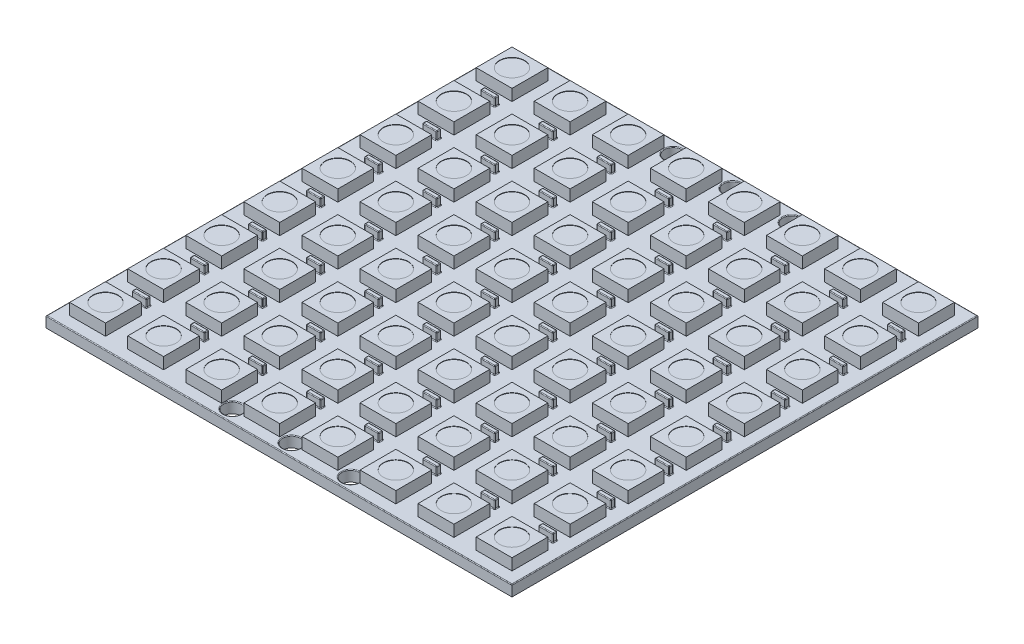
SolidWorks part; units mm, degrees
other "Cámara1"
ref_plane "Alzado" through (0, 0, 0) normal (0, 0, 1) x (1, 0, 0)
ref_plane "Planta" through (0, 0, 0) normal (0, 1, 0) x (1, 0, 0)
ref_plane "Vista lateral" through (0, 0, 0) normal (1, 0, 0) x (0, 0, -1)
sketch "Croquis1" plane through (0, 0, 0) normal (0, 1, 0) x (1, 0, 0)
  line L0 (24.25, 63.25) -> (32.5, 63.25) construction
  line L1 (0, 0) -> (65, 0)
  line L2 (0, 0) -> (0, 65)
  line L3 (0, 65) -> (65, 65)
  line L4 (65, 0) -> (65, 65)
  line L5 (32.5, 63.25) -> (40.75, 63.25) construction
  line L6 (32.5, 65) -> (32.5, 63.25) construction
  line L7 (0, 32.5) -> (65, 32.5) construction
  circle A0 centre (24.25, 63.25) radius 1.25
  circle A1 centre (32.5, 63.25) radius 1.25
  circle A2 centre (40.75, 63.25) radius 1.25
  circle A3 centre (32.5, 1.75) radius 1.25
  circle A4 centre (40.75, 1.75) radius 1.25
  circle A5 centre (24.25, 1.75) radius 1.25
  dimension "D2" = 2.5
  dimension "D4" = 24.25
  dimension "D5" = 24.25
  dimension "D1" = 65
  dimension "D3" = 1.75
extrude "Saliente-Extruir1" add sketch "Croquis1" along normal blind 1.5
sketch "Croquis2" plane through (0, 1.5, 0) normal (0, 1, 0) x (1, 0, 0)
  line L0 (0, 65) -> (0, 0) construction
  line L1 (1.65, 6.65) -> (6.65, 6.65)
  line L2 (1.65, 6.65) -> (1.65, 1.65)
  line L3 (1.65, 1.65) -> (6.65, 1.65)
  line L4 (6.65, 6.65) -> (6.65, 1.65)
  line L5 (0, 0) -> (65, 0) construction
  line L6 (9.75, 6.65) -> (9.75, 1.65)
  line L7 (9.75, 6.65) -> (14.75, 6.65)
  line L8 (14.75, 6.65) -> (14.75, 1.65)
  line L9 (9.75, 1.65) -> (14.75, 1.65)
  line L10 (17.85, 6.65) -> (17.85, 1.65)
  line L11 (17.85, 6.65) -> (22.85, 6.65)
  line L12 (22.85, 6.65) -> (22.85, 1.65)
  line L13 (17.85, 1.65) -> (22.85, 1.65)
  line L14 (25.95, 6.65) -> (25.95, 1.65)
  line L15 (25.95, 6.65) -> (30.95, 6.65)
  line L16 (30.95, 6.65) -> (30.95, 1.65)
  line L17 (25.95, 1.65) -> (30.95, 1.65)
  line L18 (34.05, 6.65) -> (34.05, 1.65)
  line L19 (34.05, 6.65) -> (39.05, 6.65)
  line L20 (39.05, 6.65) -> (39.05, 1.65)
  line L21 (34.05, 1.65) -> (39.05, 1.65)
  line L22 (42.15, 6.65) -> (42.15, 1.65)
  line L23 (42.15, 6.65) -> (47.15, 6.65)
  line L24 (47.15, 6.65) -> (47.15, 1.65)
  line L25 (42.15, 1.65) -> (47.15, 1.65)
  line L26 (50.25, 6.65) -> (50.25, 1.65)
  line L27 (50.25, 6.65) -> (55.25, 6.65)
  line L28 (55.25, 6.65) -> (55.25, 1.65)
  line L29 (50.25, 1.65) -> (55.25, 1.65)
  line L30 (58.35, 6.65) -> (58.35, 1.65)
  line L31 (58.35, 6.65) -> (63.35, 6.65)
  line L32 (63.35, 6.65) -> (63.35, 1.65)
  line L33 (58.35, 1.65) -> (63.35, 1.65)
  line L34 (9.75, 14.75) -> (9.75, 9.75)
  line L35 (9.75, 14.75) -> (14.75, 14.75)
  line L36 (14.75, 14.75) -> (14.75, 9.75)
  line L37 (9.75, 9.75) -> (14.75, 9.75)
  line L38 (17.85, 14.75) -> (17.85, 9.75)
  line L39 (17.85, 14.75) -> (22.85, 14.75)
  line L40 (22.85, 14.75) -> (22.85, 9.75)
  line L41 (17.85, 9.75) -> (22.85, 9.75)
  line L42 (25.95, 14.75) -> (25.95, 9.75)
  line L43 (25.95, 14.75) -> (30.95, 14.75)
  line L44 (30.95, 14.75) -> (30.95, 9.75)
  line L45 (25.95, 9.75) -> (30.95, 9.75)
  line L46 (34.05, 14.75) -> (34.05, 9.75)
  line L47 (34.05, 14.75) -> (39.05, 14.75)
  line L48 (39.05, 14.75) -> (39.05, 9.75)
  line L49 (34.05, 9.75) -> (39.05, 9.75)
  line L50 (42.15, 14.75) -> (42.15, 9.75)
  line L51 (42.15, 14.75) -> (47.15, 14.75)
  line L52 (47.15, 14.75) -> (47.15, 9.75)
  line L53 (42.15, 9.75) -> (47.15, 9.75)
  line L54 (50.25, 14.75) -> (50.25, 9.75)
  line L55 (50.25, 14.75) -> (55.25, 14.75)
  line L56 (55.25, 14.75) -> (55.25, 9.75)
  line L57 (50.25, 9.75) -> (55.25, 9.75)
  line L58 (58.35, 14.75) -> (58.35, 9.75)
  line L59 (58.35, 14.75) -> (63.35, 14.75)
  line L60 (63.35, 14.75) -> (63.35, 9.75)
  line L61 (58.35, 9.75) -> (63.35, 9.75)
  line L62 (9.75, 22.85) -> (9.75, 17.85)
  line L63 (9.75, 22.85) -> (14.75, 22.85)
  line L64 (14.75, 22.85) -> (14.75, 17.85)
  line L65 (9.75, 17.85) -> (14.75, 17.85)
  line L66 (17.85, 22.85) -> (17.85, 17.85)
  line L67 (17.85, 22.85) -> (22.85, 22.85)
  line L68 (22.85, 22.85) -> (22.85, 17.85)
  line L69 (17.85, 17.85) -> (22.85, 17.85)
  line L70 (25.95, 22.85) -> (25.95, 17.85)
  line L71 (25.95, 22.85) -> (30.95, 22.85)
  line L72 (30.95, 22.85) -> (30.95, 17.85)
  line L73 (25.95, 17.85) -> (30.95, 17.85)
  line L74 (34.05, 22.85) -> (34.05, 17.85)
  line L75 (34.05, 22.85) -> (39.05, 22.85)
  line L76 (39.05, 22.85) -> (39.05, 17.85)
  line L77 (34.05, 17.85) -> (39.05, 17.85)
  line L78 (42.15, 22.85) -> (42.15, 17.85)
  line L79 (42.15, 22.85) -> (47.15, 22.85)
  line L80 (47.15, 22.85) -> (47.15, 17.85)
  line L81 (42.15, 17.85) -> (47.15, 17.85)
  line L82 (50.25, 22.85) -> (50.25, 17.85)
  line L83 (50.25, 22.85) -> (55.25, 22.85)
  line L84 (55.25, 22.85) -> (55.25, 17.85)
  line L85 (50.25, 17.85) -> (55.25, 17.85)
  line L86 (58.35, 22.85) -> (58.35, 17.85)
  line L87 (58.35, 22.85) -> (63.35, 22.85)
  line L88 (63.35, 22.85) -> (63.35, 17.85)
  line L89 (58.35, 17.85) -> (63.35, 17.85)
  line L90 (9.75, 30.95) -> (9.75, 25.95)
  line L91 (9.75, 30.95) -> (14.75, 30.95)
  line L92 (14.75, 30.95) -> (14.75, 25.95)
  line L93 (9.75, 25.95) -> (14.75, 25.95)
  line L94 (17.85, 30.95) -> (17.85, 25.95)
  line L95 (17.85, 30.95) -> (22.85, 30.95)
  line L96 (22.85, 30.95) -> (22.85, 25.95)
  line L97 (17.85, 25.95) -> (22.85, 25.95)
  line L98 (25.95, 30.95) -> (25.95, 25.95)
  line L99 (25.95, 30.95) -> (30.95, 30.95)
  line L100 (30.95, 30.95) -> (30.95, 25.95)
  line L101 (25.95, 25.95) -> (30.95, 25.95)
  line L102 (34.05, 30.95) -> (34.05, 25.95)
  line L103 (34.05, 30.95) -> (39.05, 30.95)
  line L104 (39.05, 30.95) -> (39.05, 25.95)
  line L105 (34.05, 25.95) -> (39.05, 25.95)
  line L106 (42.15, 30.95) -> (42.15, 25.95)
  line L107 (42.15, 30.95) -> (47.15, 30.95)
  line L108 (47.15, 30.95) -> (47.15, 25.95)
  line L109 (42.15, 25.95) -> (47.15, 25.95)
  line L110 (50.25, 30.95) -> (50.25, 25.95)
  line L111 (50.25, 30.95) -> (55.25, 30.95)
  line L112 (55.25, 30.95) -> (55.25, 25.95)
  line L113 (50.25, 25.95) -> (55.25, 25.95)
  line L114 (58.35, 30.95) -> (58.35, 25.95)
  line L115 (58.35, 30.95) -> (63.35, 30.95)
  line L116 (63.35, 30.95) -> (63.35, 25.95)
  line L117 (58.35, 25.95) -> (63.35, 25.95)
  line L118 (9.75, 39.05) -> (9.75, 34.05)
  line L119 (9.75, 39.05) -> (14.75, 39.05)
  line L120 (14.75, 39.05) -> (14.75, 34.05)
  line L121 (9.75, 34.05) -> (14.75, 34.05)
  line L122 (17.85, 39.05) -> (17.85, 34.05)
  line L123 (17.85, 39.05) -> (22.85, 39.05)
  line L124 (22.85, 39.05) -> (22.85, 34.05)
  line L125 (17.85, 34.05) -> (22.85, 34.05)
  line L126 (25.95, 39.05) -> (25.95, 34.05)
  line L127 (25.95, 39.05) -> (30.95, 39.05)
  line L128 (30.95, 39.05) -> (30.95, 34.05)
  line L129 (25.95, 34.05) -> (30.95, 34.05)
  line L130 (34.05, 39.05) -> (34.05, 34.05)
  line L131 (34.05, 39.05) -> (39.05, 39.05)
  line L132 (39.05, 39.05) -> (39.05, 34.05)
  line L133 (34.05, 34.05) -> (39.05, 34.05)
  line L134 (42.15, 39.05) -> (42.15, 34.05)
  line L135 (42.15, 39.05) -> (47.15, 39.05)
  line L136 (47.15, 39.05) -> (47.15, 34.05)
  line L137 (42.15, 34.05) -> (47.15, 34.05)
  line L138 (50.25, 39.05) -> (50.25, 34.05)
  line L139 (50.25, 39.05) -> (55.25, 39.05)
  line L140 (55.25, 39.05) -> (55.25, 34.05)
  line L141 (50.25, 34.05) -> (55.25, 34.05)
  line L142 (58.35, 39.05) -> (58.35, 34.05)
  line L143 (58.35, 39.05) -> (63.35, 39.05)
  line L144 (63.35, 39.05) -> (63.35, 34.05)
  line L145 (58.35, 34.05) -> (63.35, 34.05)
  line L146 (9.75, 47.15) -> (9.75, 42.15)
  line L147 (9.75, 47.15) -> (14.75, 47.15)
  line L148 (14.75, 47.15) -> (14.75, 42.15)
  line L149 (9.75, 42.15) -> (14.75, 42.15)
  line L150 (17.85, 47.15) -> (17.85, 42.15)
  line L151 (17.85, 47.15) -> (22.85, 47.15)
  line L152 (22.85, 47.15) -> (22.85, 42.15)
  line L153 (17.85, 42.15) -> (22.85, 42.15)
  line L154 (25.95, 47.15) -> (25.95, 42.15)
  line L155 (25.95, 47.15) -> (30.95, 47.15)
  line L156 (30.95, 47.15) -> (30.95, 42.15)
  line L157 (25.95, 42.15) -> (30.95, 42.15)
  line L158 (34.05, 47.15) -> (34.05, 42.15)
  line L159 (34.05, 47.15) -> (39.05, 47.15)
  line L160 (39.05, 47.15) -> (39.05, 42.15)
  line L161 (34.05, 42.15) -> (39.05, 42.15)
  line L162 (42.15, 47.15) -> (42.15, 42.15)
  line L163 (42.15, 47.15) -> (47.15, 47.15)
  line L164 (47.15, 47.15) -> (47.15, 42.15)
  line L165 (42.15, 42.15) -> (47.15, 42.15)
  line L166 (50.25, 47.15) -> (50.25, 42.15)
  line L167 (50.25, 47.15) -> (55.25, 47.15)
  line L168 (55.25, 47.15) -> (55.25, 42.15)
  line L169 (50.25, 42.15) -> (55.25, 42.15)
  line L170 (58.35, 47.15) -> (58.35, 42.15)
  line L171 (58.35, 47.15) -> (63.35, 47.15)
  line L172 (63.35, 47.15) -> (63.35, 42.15)
  line L173 (58.35, 42.15) -> (63.35, 42.15)
  line L174 (9.75, 55.25) -> (9.75, 50.25)
  line L175 (9.75, 55.25) -> (14.75, 55.25)
  line L176 (14.75, 55.25) -> (14.75, 50.25)
  line L177 (9.75, 50.25) -> (14.75, 50.25)
  line L178 (17.85, 55.25) -> (17.85, 50.25)
  line L179 (17.85, 55.25) -> (22.85, 55.25)
  line L180 (22.85, 55.25) -> (22.85, 50.25)
  line L181 (17.85, 50.25) -> (22.85, 50.25)
  line L182 (25.95, 55.25) -> (25.95, 50.25)
  line L183 (25.95, 55.25) -> (30.95, 55.25)
  line L184 (30.95, 55.25) -> (30.95, 50.25)
  line L185 (25.95, 50.25) -> (30.95, 50.25)
  line L186 (34.05, 55.25) -> (34.05, 50.25)
  line L187 (34.05, 55.25) -> (39.05, 55.25)
  line L188 (39.05, 55.25) -> (39.05, 50.25)
  line L189 (34.05, 50.25) -> (39.05, 50.25)
  line L190 (42.15, 55.25) -> (42.15, 50.25)
  line L191 (42.15, 55.25) -> (47.15, 55.25)
  line L192 (47.15, 55.25) -> (47.15, 50.25)
  line L193 (42.15, 50.25) -> (47.15, 50.25)
  line L194 (50.25, 55.25) -> (50.25, 50.25)
  line L195 (50.25, 55.25) -> (55.25, 55.25)
  line L196 (55.25, 55.25) -> (55.25, 50.25)
  line L197 (50.25, 50.25) -> (55.25, 50.25)
  line L198 (58.35, 55.25) -> (58.35, 50.25)
  line L199 (58.35, 55.25) -> (63.35, 55.25)
  line L200 (63.35, 55.25) -> (63.35, 50.25)
  line L201 (58.35, 50.25) -> (63.35, 50.25)
  line L202 (9.75, 63.35) -> (9.75, 58.35)
  line L203 (9.75, 63.35) -> (14.75, 63.35)
  line L204 (14.75, 63.35) -> (14.75, 58.35)
  line L205 (9.75, 58.35) -> (14.75, 58.35)
  line L206 (17.85, 63.35) -> (17.85, 58.35)
  line L207 (17.85, 63.35) -> (22.85, 63.35)
  line L208 (22.85, 63.35) -> (22.85, 58.35)
  line L209 (17.85, 58.35) -> (22.85, 58.35)
  line L210 (25.95, 63.35) -> (25.95, 58.35)
  line L211 (25.95, 63.35) -> (30.95, 63.35)
  line L212 (30.95, 63.35) -> (30.95, 58.35)
  line L213 (25.95, 58.35) -> (30.95, 58.35)
  line L214 (34.05, 63.35) -> (34.05, 58.35)
  line L215 (34.05, 63.35) -> (39.05, 63.35)
  line L216 (39.05, 63.35) -> (39.05, 58.35)
  line L217 (34.05, 58.35) -> (39.05, 58.35)
  line L218 (42.15, 63.35) -> (42.15, 58.35)
  line L219 (42.15, 63.35) -> (47.15, 63.35)
  line L220 (47.15, 63.35) -> (47.15, 58.35)
  line L221 (42.15, 58.35) -> (47.15, 58.35)
  line L222 (50.25, 63.35) -> (50.25, 58.35)
  line L223 (50.25, 63.35) -> (55.25, 63.35)
  line L224 (55.25, 63.35) -> (55.25, 58.35)
  line L225 (50.25, 58.35) -> (55.25, 58.35)
  line L226 (58.35, 63.35) -> (58.35, 58.35)
  line L227 (58.35, 63.35) -> (63.35, 63.35)
  line L228 (63.35, 63.35) -> (63.35, 58.35)
  line L229 (58.35, 58.35) -> (63.35, 58.35)
  line L230 (1.65, 14.75) -> (1.65, 9.75)
  line L231 (1.65, 14.75) -> (6.65, 14.75)
  line L232 (6.65, 14.75) -> (6.65, 9.75)
  line L233 (1.65, 9.75) -> (6.65, 9.75)
  line L234 (1.65, 22.85) -> (1.65, 17.85)
  line L235 (1.65, 22.85) -> (6.65, 22.85)
  line L236 (6.65, 22.85) -> (6.65, 17.85)
  line L237 (1.65, 17.85) -> (6.65, 17.85)
  line L238 (1.65, 30.95) -> (1.65, 25.95)
  line L239 (1.65, 30.95) -> (6.65, 30.95)
  line L240 (6.65, 30.95) -> (6.65, 25.95)
  line L241 (1.65, 25.95) -> (6.65, 25.95)
  line L242 (1.65, 39.05) -> (1.65, 34.05)
  line L243 (1.65, 39.05) -> (6.65, 39.05)
  line L244 (6.65, 39.05) -> (6.65, 34.05)
  line L245 (1.65, 34.05) -> (6.65, 34.05)
  line L246 (1.65, 47.15) -> (1.65, 42.15)
  line L247 (1.65, 47.15) -> (6.65, 47.15)
  line L248 (6.65, 47.15) -> (6.65, 42.15)
  line L249 (1.65, 42.15) -> (6.65, 42.15)
  line L250 (1.65, 55.25) -> (1.65, 50.25)
  line L251 (1.65, 55.25) -> (6.65, 55.25)
  line L252 (6.65, 55.25) -> (6.65, 50.25)
  line L253 (1.65, 50.25) -> (6.65, 50.25)
  line L254 (1.65, 63.35) -> (1.65, 58.35)
  line L255 (1.65, 63.35) -> (6.65, 63.35)
  line L256 (6.65, 63.35) -> (6.65, 58.35)
  line L257 (1.65, 58.35) -> (6.65, 58.35)
  dimension "D1" = 5
  dimension "D2" = 1.65
  dimension "D3" = 1.65
  dimension "D4" = 8
  dimension "D5" = 8
extrude "Saliente-Extruir2" add sketch "Croquis2" along normal blind 1.6 separate body
sketch "Croquis3" plane through (0, 3.1, 0) normal (0, 1, 0) x (1, 0, 0)
  line L0 (4.15, 4.15) -> (12.25, 4.15) construction
  line L1 (4.15, 4.15) -> (4.15, 12.25) construction
  circle A0 centre (4.15, 4.15) radius 1.75
  circle A1 centre (12.25, 4.15) radius 1.75
  circle A2 centre (20.35, 4.15) radius 1.75
  circle A3 centre (28.45, 4.15) radius 1.75
  circle A4 centre (36.55, 4.15) radius 1.75
  circle A5 centre (44.65, 4.15) radius 1.75
  circle A6 centre (52.75, 4.15) radius 1.75
  circle A7 centre (60.85, 4.15) radius 1.75
  circle A8 centre (12.25, 12.25) radius 1.75
  circle A9 centre (20.35, 12.25) radius 1.75
  circle A10 centre (28.45, 12.25) radius 1.75
  circle A11 centre (36.55, 12.25) radius 1.75
  circle A12 centre (44.65, 12.25) radius 1.75
  circle A13 centre (52.75, 12.25) radius 1.75
  circle A14 centre (60.85, 12.25) radius 1.75
  circle A15 centre (12.25, 20.35) radius 1.75
  circle A16 centre (20.35, 20.35) radius 1.75
  circle A17 centre (28.45, 20.35) radius 1.75
  circle A18 centre (36.55, 20.35) radius 1.75
  circle A19 centre (44.65, 20.35) radius 1.75
  circle A20 centre (52.75, 20.35) radius 1.75
  circle A21 centre (60.85, 20.35) radius 1.75
  circle A22 centre (12.25, 28.45) radius 1.75
  circle A23 centre (20.35, 28.45) radius 1.75
  circle A24 centre (28.45, 28.45) radius 1.75
  circle A25 centre (36.55, 28.45) radius 1.75
  circle A26 centre (44.65, 28.45) radius 1.75
  circle A27 centre (52.75, 28.45) radius 1.75
  circle A28 centre (60.85, 28.45) radius 1.75
  circle A29 centre (12.25, 36.55) radius 1.75
  circle A30 centre (20.35, 36.55) radius 1.75
  circle A31 centre (28.45, 36.55) radius 1.75
  circle A32 centre (36.55, 36.55) radius 1.75
  circle A33 centre (44.65, 36.55) radius 1.75
  circle A34 centre (52.75, 36.55) radius 1.75
  circle A35 centre (60.85, 36.55) radius 1.75
  circle A36 centre (12.25, 44.65) radius 1.75
  circle A37 centre (20.35, 44.65) radius 1.75
  circle A38 centre (28.45, 44.65) radius 1.75
  circle A39 centre (36.55, 44.65) radius 1.75
  circle A40 centre (44.65, 44.65) radius 1.75
  circle A41 centre (52.75, 44.65) radius 1.75
  circle A42 centre (60.85, 44.65) radius 1.75
  circle A43 centre (12.25, 52.75) radius 1.75
  circle A44 centre (20.35, 52.75) radius 1.75
  circle A45 centre (28.45, 52.75) radius 1.75
  circle A46 centre (36.55, 52.75) radius 1.75
  circle A47 centre (44.65, 52.75) radius 1.75
  circle A48 centre (52.75, 52.75) radius 1.75
  circle A49 centre (60.85, 52.75) radius 1.75
  circle A50 centre (12.25, 60.85) radius 1.75
  circle A51 centre (20.35, 60.85) radius 1.75
  circle A52 centre (28.45, 60.85) radius 1.75
  circle A53 centre (36.55, 60.85) radius 1.75
  circle A54 centre (44.65, 60.85) radius 1.75
  circle A55 centre (52.75, 60.85) radius 1.75
  circle A56 centre (60.85, 60.85) radius 1.75
  circle A57 centre (4.15, 12.25) radius 1.75
  circle A58 centre (4.15, 20.35) radius 1.75
  circle A59 centre (4.15, 28.45) radius 1.75
  circle A60 centre (4.15, 36.55) radius 1.75
  circle A61 centre (4.15, 44.65) radius 1.75
  circle A62 centre (4.15, 52.75) radius 1.75
  circle A63 centre (4.15, 60.85) radius 1.75
  dimension "D1" = 3.5
  dimension "D4" = 8.1
  dimension "D5" = 8.1
  dimension "D2" = 8
  dimension "D3" = 8
extrude "Cortar-Extruir1" cut sketch "Croquis3" against normal blind 0.05
sketch "Croquis4" plane through (0, 1.5, 0) normal (0, 1, 0) x (1, 0, 0)
  line L0 (6.65, 9.75) -> (6.65, 6.65) construction
  line L1 (6.65, 8.2) -> (0, 8.2) construction
  line L2 (0, 65) -> (0, 0) construction
  line L3 (12.2, 7.9) -> (12.2, 8.5)
  line L4 (4.1, 7.9) -> (6.1, 7.9)
  line L5 (4.1, 7.9) -> (4.1, 8.5)
  line L6 (4.1, 8.5) -> (6.1, 8.5)
  line L7 (6.1, 7.9) -> (6.1, 8.5)
  line L8 (5.1, 8.5) -> (5.1, 7.9) construction
  line L9 (4.1, 8.2) -> (6.65, 8.2) construction
  line L10 (12.2, 7.9) -> (14.2, 7.9)
  line L11 (14.2, 7.9) -> (14.2, 8.5)
  line L12 (12.2, 8.5) -> (14.2, 8.5)
  line L13 (20.3, 7.9) -> (20.3, 8.5)
  line L14 (20.3, 7.9) -> (22.3, 7.9)
  line L15 (22.3, 7.9) -> (22.3, 8.5)
  line L16 (20.3, 8.5) -> (22.3, 8.5)
  line L17 (28.4, 7.9) -> (28.4, 8.5)
  line L18 (28.4, 7.9) -> (30.4, 7.9)
  line L19 (30.4, 7.9) -> (30.4, 8.5)
  line L20 (28.4, 8.5) -> (30.4, 8.5)
  line L21 (36.5, 7.9) -> (36.5, 8.5)
  line L22 (36.5, 7.9) -> (38.5, 7.9)
  line L23 (38.5, 7.9) -> (38.5, 8.5)
  line L24 (36.5, 8.5) -> (38.5, 8.5)
  line L25 (44.6, 7.9) -> (44.6, 8.5)
  line L26 (44.6, 7.9) -> (46.6, 7.9)
  line L27 (46.6, 7.9) -> (46.6, 8.5)
  line L28 (44.6, 8.5) -> (46.6, 8.5)
  line L29 (52.7, 7.9) -> (52.7, 8.5)
  line L30 (52.7, 7.9) -> (54.7, 7.9)
  line L31 (54.7, 7.9) -> (54.7, 8.5)
  line L32 (52.7, 8.5) -> (54.7, 8.5)
  line L33 (60.8, 7.9) -> (60.8, 8.5)
  line L34 (60.8, 7.9) -> (62.8, 7.9)
  line L35 (62.8, 7.9) -> (62.8, 8.5)
  line L36 (60.8, 8.5) -> (62.8, 8.5)
  line L37 (12.2, 16) -> (12.2, 16.6)
  line L38 (12.2, 16) -> (14.2, 16)
  line L39 (14.2, 16) -> (14.2, 16.6)
  line L40 (12.2, 16.6) -> (14.2, 16.6)
  line L41 (20.3, 16) -> (20.3, 16.6)
  line L42 (20.3, 16) -> (22.3, 16)
  line L43 (22.3, 16) -> (22.3, 16.6)
  line L44 (20.3, 16.6) -> (22.3, 16.6)
  line L45 (28.4, 16) -> (28.4, 16.6)
  line L46 (28.4, 16) -> (30.4, 16)
  line L47 (30.4, 16) -> (30.4, 16.6)
  line L48 (28.4, 16.6) -> (30.4, 16.6)
  line L49 (36.5, 16) -> (36.5, 16.6)
  line L50 (36.5, 16) -> (38.5, 16)
  line L51 (38.5, 16) -> (38.5, 16.6)
  line L52 (36.5, 16.6) -> (38.5, 16.6)
  line L53 (44.6, 16) -> (44.6, 16.6)
  line L54 (44.6, 16) -> (46.6, 16)
  line L55 (46.6, 16) -> (46.6, 16.6)
  line L56 (44.6, 16.6) -> (46.6, 16.6)
  line L57 (52.7, 16) -> (52.7, 16.6)
  line L58 (52.7, 16) -> (54.7, 16)
  line L59 (54.7, 16) -> (54.7, 16.6)
  line L60 (52.7, 16.6) -> (54.7, 16.6)
  line L61 (60.8, 16) -> (60.8, 16.6)
  line L62 (60.8, 16) -> (62.8, 16)
  line L63 (62.8, 16) -> (62.8, 16.6)
  line L64 (60.8, 16.6) -> (62.8, 16.6)
  line L65 (12.2, 24.1) -> (12.2, 24.7)
  line L66 (12.2, 24.1) -> (14.2, 24.1)
  line L67 (14.2, 24.1) -> (14.2, 24.7)
  line L68 (12.2, 24.7) -> (14.2, 24.7)
  line L69 (20.3, 24.1) -> (20.3, 24.7)
  line L70 (20.3, 24.1) -> (22.3, 24.1)
  line L71 (22.3, 24.1) -> (22.3, 24.7)
  line L72 (20.3, 24.7) -> (22.3, 24.7)
  line L73 (28.4, 24.1) -> (28.4, 24.7)
  line L74 (28.4, 24.1) -> (30.4, 24.1)
  line L75 (30.4, 24.1) -> (30.4, 24.7)
  line L76 (28.4, 24.7) -> (30.4, 24.7)
  line L77 (36.5, 24.1) -> (36.5, 24.7)
  line L78 (36.5, 24.1) -> (38.5, 24.1)
  line L79 (38.5, 24.1) -> (38.5, 24.7)
  line L80 (36.5, 24.7) -> (38.5, 24.7)
  line L81 (44.6, 24.1) -> (44.6, 24.7)
  line L82 (44.6, 24.1) -> (46.6, 24.1)
  line L83 (46.6, 24.1) -> (46.6, 24.7)
  line L84 (44.6, 24.7) -> (46.6, 24.7)
  line L85 (52.7, 24.1) -> (52.7, 24.7)
  line L86 (52.7, 24.1) -> (54.7, 24.1)
  line L87 (54.7, 24.1) -> (54.7, 24.7)
  line L88 (52.7, 24.7) -> (54.7, 24.7)
  line L89 (60.8, 24.1) -> (60.8, 24.7)
  line L90 (60.8, 24.1) -> (62.8, 24.1)
  line L91 (62.8, 24.1) -> (62.8, 24.7)
  line L92 (60.8, 24.7) -> (62.8, 24.7)
  line L93 (12.2, 32.2) -> (12.2, 32.8)
  line L94 (12.2, 32.2) -> (14.2, 32.2)
  line L95 (14.2, 32.2) -> (14.2, 32.8)
  line L96 (12.2, 32.8) -> (14.2, 32.8)
  line L97 (20.3, 32.2) -> (20.3, 32.8)
  line L98 (20.3, 32.2) -> (22.3, 32.2)
  line L99 (22.3, 32.2) -> (22.3, 32.8)
  line L100 (20.3, 32.8) -> (22.3, 32.8)
  line L101 (28.4, 32.2) -> (28.4, 32.8)
  line L102 (28.4, 32.2) -> (30.4, 32.2)
  line L103 (30.4, 32.2) -> (30.4, 32.8)
  line L104 (28.4, 32.8) -> (30.4, 32.8)
  line L105 (36.5, 32.2) -> (36.5, 32.8)
  line L106 (36.5, 32.2) -> (38.5, 32.2)
  line L107 (38.5, 32.2) -> (38.5, 32.8)
  line L108 (36.5, 32.8) -> (38.5, 32.8)
  line L109 (44.6, 32.2) -> (44.6, 32.8)
  line L110 (44.6, 32.2) -> (46.6, 32.2)
  line L111 (46.6, 32.2) -> (46.6, 32.8)
  line L112 (44.6, 32.8) -> (46.6, 32.8)
  line L113 (52.7, 32.2) -> (52.7, 32.8)
  line L114 (52.7, 32.2) -> (54.7, 32.2)
  line L115 (54.7, 32.2) -> (54.7, 32.8)
  line L116 (52.7, 32.8) -> (54.7, 32.8)
  line L117 (60.8, 32.2) -> (60.8, 32.8)
  line L118 (60.8, 32.2) -> (62.8, 32.2)
  line L119 (62.8, 32.2) -> (62.8, 32.8)
  line L120 (60.8, 32.8) -> (62.8, 32.8)
  line L121 (12.2, 40.3) -> (12.2, 40.9)
  line L122 (12.2, 40.3) -> (14.2, 40.3)
  line L123 (14.2, 40.3) -> (14.2, 40.9)
  line L124 (12.2, 40.9) -> (14.2, 40.9)
  line L125 (20.3, 40.3) -> (20.3, 40.9)
  line L126 (20.3, 40.3) -> (22.3, 40.3)
  line L127 (22.3, 40.3) -> (22.3, 40.9)
  line L128 (20.3, 40.9) -> (22.3, 40.9)
  line L129 (28.4, 40.3) -> (28.4, 40.9)
  line L130 (28.4, 40.3) -> (30.4, 40.3)
  line L131 (30.4, 40.3) -> (30.4, 40.9)
  line L132 (28.4, 40.9) -> (30.4, 40.9)
  line L133 (36.5, 40.3) -> (36.5, 40.9)
  line L134 (36.5, 40.3) -> (38.5, 40.3)
  line L135 (38.5, 40.3) -> (38.5, 40.9)
  line L136 (36.5, 40.9) -> (38.5, 40.9)
  line L137 (44.6, 40.3) -> (44.6, 40.9)
  line L138 (44.6, 40.3) -> (46.6, 40.3)
  line L139 (46.6, 40.3) -> (46.6, 40.9)
  line L140 (44.6, 40.9) -> (46.6, 40.9)
  line L141 (52.7, 40.3) -> (52.7, 40.9)
  line L142 (52.7, 40.3) -> (54.7, 40.3)
  line L143 (54.7, 40.3) -> (54.7, 40.9)
  line L144 (52.7, 40.9) -> (54.7, 40.9)
  line L145 (60.8, 40.3) -> (60.8, 40.9)
  line L146 (60.8, 40.3) -> (62.8, 40.3)
  line L147 (62.8, 40.3) -> (62.8, 40.9)
  line L148 (60.8, 40.9) -> (62.8, 40.9)
  line L149 (12.2, 48.4) -> (12.2, 49)
  line L150 (12.2, 48.4) -> (14.2, 48.4)
  line L151 (14.2, 48.4) -> (14.2, 49)
  line L152 (12.2, 49) -> (14.2, 49)
  line L153 (20.3, 48.4) -> (20.3, 49)
  line L154 (20.3, 48.4) -> (22.3, 48.4)
  line L155 (22.3, 48.4) -> (22.3, 49)
  line L156 (20.3, 49) -> (22.3, 49)
  line L157 (28.4, 48.4) -> (28.4, 49)
  line L158 (28.4, 48.4) -> (30.4, 48.4)
  line L159 (30.4, 48.4) -> (30.4, 49)
  line L160 (28.4, 49) -> (30.4, 49)
  line L161 (36.5, 48.4) -> (36.5, 49)
  line L162 (36.5, 48.4) -> (38.5, 48.4)
  line L163 (38.5, 48.4) -> (38.5, 49)
  line L164 (36.5, 49) -> (38.5, 49)
  line L165 (44.6, 48.4) -> (44.6, 49)
  line L166 (44.6, 48.4) -> (46.6, 48.4)
  line L167 (46.6, 48.4) -> (46.6, 49)
  line L168 (44.6, 49) -> (46.6, 49)
  line L169 (52.7, 48.4) -> (52.7, 49)
  line L170 (52.7, 48.4) -> (54.7, 48.4)
  line L171 (54.7, 48.4) -> (54.7, 49)
  line L172 (52.7, 49) -> (54.7, 49)
  line L173 (60.8, 48.4) -> (60.8, 49)
  line L174 (60.8, 48.4) -> (62.8, 48.4)
  line L175 (62.8, 48.4) -> (62.8, 49)
  line L176 (60.8, 49) -> (62.8, 49)
  line L177 (12.2, 56.5) -> (12.2, 57.1)
  line L178 (12.2, 56.5) -> (14.2, 56.5)
  line L179 (14.2, 56.5) -> (14.2, 57.1)
  line L180 (12.2, 57.1) -> (14.2, 57.1)
  line L181 (20.3, 56.5) -> (20.3, 57.1)
  line L182 (20.3, 56.5) -> (22.3, 56.5)
  line L183 (22.3, 56.5) -> (22.3, 57.1)
  line L184 (20.3, 57.1) -> (22.3, 57.1)
  line L185 (28.4, 56.5) -> (28.4, 57.1)
  line L186 (28.4, 56.5) -> (30.4, 56.5)
  line L187 (30.4, 56.5) -> (30.4, 57.1)
  line L188 (28.4, 57.1) -> (30.4, 57.1)
  line L189 (36.5, 56.5) -> (36.5, 57.1)
  line L190 (36.5, 56.5) -> (38.5, 56.5)
  line L191 (38.5, 56.5) -> (38.5, 57.1)
  line L192 (36.5, 57.1) -> (38.5, 57.1)
  line L193 (44.6, 56.5) -> (44.6, 57.1)
  line L194 (44.6, 56.5) -> (46.6, 56.5)
  line L195 (46.6, 56.5) -> (46.6, 57.1)
  line L196 (44.6, 57.1) -> (46.6, 57.1)
  line L197 (52.7, 56.5) -> (52.7, 57.1)
  line L198 (52.7, 56.5) -> (54.7, 56.5)
  line L199 (54.7, 56.5) -> (54.7, 57.1)
  line L200 (52.7, 57.1) -> (54.7, 57.1)
  line L201 (60.8, 56.5) -> (60.8, 57.1)
  line L202 (60.8, 56.5) -> (62.8, 56.5)
  line L203 (62.8, 56.5) -> (62.8, 57.1)
  line L204 (60.8, 57.1) -> (62.8, 57.1)
  line L205 (4.1, 16) -> (4.1, 16.6)
  line L206 (4.1, 16) -> (6.1, 16)
  line L207 (6.1, 16) -> (6.1, 16.6)
  line L208 (4.1, 16.6) -> (6.1, 16.6)
  line L209 (4.1, 24.1) -> (4.1, 24.7)
  line L210 (4.1, 24.1) -> (6.1, 24.1)
  line L211 (6.1, 24.1) -> (6.1, 24.7)
  line L212 (4.1, 24.7) -> (6.1, 24.7)
  line L213 (4.1, 32.2) -> (4.1, 32.8)
  line L214 (4.1, 32.2) -> (6.1, 32.2)
  line L215 (6.1, 32.2) -> (6.1, 32.8)
  line L216 (4.1, 32.8) -> (6.1, 32.8)
  line L217 (4.1, 40.3) -> (4.1, 40.9)
  line L218 (4.1, 40.3) -> (6.1, 40.3)
  line L219 (6.1, 40.3) -> (6.1, 40.9)
  line L220 (4.1, 40.9) -> (6.1, 40.9)
  line L221 (4.1, 48.4) -> (4.1, 49)
  line L222 (4.1, 48.4) -> (6.1, 48.4)
  line L223 (6.1, 48.4) -> (6.1, 49)
  line L224 (4.1, 49) -> (6.1, 49)
  line L225 (4.1, 56.5) -> (4.1, 57.1)
  line L226 (4.1, 56.5) -> (6.1, 56.5)
  line L227 (6.1, 56.5) -> (6.1, 57.1)
  line L228 (4.1, 57.1) -> (6.1, 57.1)
  line L229 (4.1, 7.9) -> (12.2, 7.9) construction
  point P8 (5.1, 8.2)
  dimension "D1" = 0.6
  dimension "D2" = 2
  dimension "D3" = 1.1
  dimension "D6" = 8.1
  dimension "D4" = 8
  dimension "D5" = 7
extrude "Saliente-Extruir3" add sketch "Croquis4" along normal blind 1.1
fillet "Redondeo1" radius 0.1 400 edges at (5.1, 2.6, -7.9) (4.1, 2.6, -8.2) (5.1, 2.6, -8.5) (6.1, 2.6, -8.2) (4.1, 1.5, -56.8) (5.1, 1.5, -56.5) (6.1, 1.5, -56.8) (5.1, 1.5, -57.1) (4.1, 1.5, -40.6) (5.1, 1.5, -40.3) (6.1, 1.5, -40.6) (5.1, 1.5, -40.9) (4.1, 1.5, -24.4) (5.1, 1.5, -24.1) (6.1, 1.5, -24.4) (5.1, 1.5, -24.7) (60.8, 1.5, -56.8) (61.8, 1.5, -56.5) (62.8, 1.5, -56.8) (61.8, 1.5, -57.1) (44.6, 1.5, -56.8) (45.6, 1.5, -56.5) (46.6, 1.5, -56.8) (45.6, 1.5, -57.1) (28.4, 1.5, -56.8) (29.4, 1.5, -56.5) (30.4, 1.5, -56.8) (29.4, 1.5, -57.1) (12.2, 1.5, -56.8) (13.2, 1.5, -56.5) (14.2, 1.5, -56.8) (13.2, 1.5, -57.1) (52.7, 1.5, -48.7) (53.7, 1.5, -48.4) (54.7, 1.5, -48.7) (53.7, 1.5, -49) (36.5, 1.5, -48.7) (37.5, 1.5, -48.4) (38.5, 1.5, -48.7) (37.5, 1.5, -49) (20.3, 1.5, -48.7) (21.3, 1.5, -48.4) (22.3, 1.5, -48.7) (21.3, 1.5, -49) (60.8, 1.5, -40.6) (61.8, 1.5, -40.3) (62.8, 1.5, -40.6) (61.8, 1.5, -40.9) (44.6, 1.5, -40.6) (45.6, 1.5, -40.3) (46.6, 1.5, -40.6) (45.6, 1.5, -40.9) (28.4, 1.5, -40.6) (29.4, 1.5, -40.3) (30.4, 1.5, -40.6) (29.4, 1.5, -40.9) (12.2, 1.5, -40.6) (13.2, 1.5, -40.3) (14.2, 1.5, -40.6) (13.2, 1.5, -40.9) (52.7, 1.5, -32.5) (53.7, 1.5, -32.2) (54.7, 1.5, -32.5) (53.7, 1.5, -32.8) (36.5, 1.5, -32.5) (37.5, 1.5, -32.2) (38.5, 1.5, -32.5) (37.5, 1.5, -32.8) (20.3, 1.5, -32.5) (21.3, 1.5, -32.2) (22.3, 1.5, -32.5) (21.3, 1.5, -32.8) (60.8, 1.5, -24.4) (61.8, 1.5, -24.1) (62.8, 1.5, -24.4) (61.8, 1.5, -24.7) (44.6, 1.5, -24.4) (45.6, 1.5, -24.1) (46.6, 1.5, -24.4) (45.6, 1.5, -24.7) (28.4, 1.5, -24.4) (29.4, 1.5, -24.1) (30.4, 1.5, -24.4) (29.4, 1.5, -24.7) (12.2, 1.5, -24.4) (13.2, 1.5, -24.1) (14.2, 1.5, -24.4) (13.2, 1.5, -24.7) (52.7, 1.5, -16.3) (53.7, 1.5, -16) (54.7, 1.5, -16.3) (53.7, 1.5, -16.6) (36.5, 1.5, -16.3) (37.5, 1.5, -16) (38.5, 1.5, -16.3) (37.5, 1.5, -16.6) (20.3, 1.5, -16.3) (21.3, 1.5, -16) (22.3, 1.5, -16.3) (21.3, 1.5, -16.6) (60.8, 1.5, -8.2) (61.8, 1.5, -7.9) (62.8, 1.5, -8.2) (61.8, 1.5, -8.5) (44.6, 1.5, -8.2) (45.6, 1.5, -7.9) (46.6, 1.5, -8.2) (45.6, 1.5, -8.5) (28.4, 1.5, -8.2) (29.4, 1.5, -7.9) (30.4, 1.5, -8.2) (29.4, 1.5, -8.5) (12.2, 1.5, -8.2) (13.2, 1.5, -7.9) (14.2, 1.5, -8.2) (13.2, 1.5, -8.5) (24.25, 1.5, -3) (40.75, 1.5, -3) (32.5, 1.5, -3) (40.75, 1.5, -62) (32.5, 1.5, -62) (24.25, 1.5, -62) (32.5, 1.5, -65) (65, 1.5, -32.5) (32.5, 1.5, 0) (0, 1.5, -32.5) (5.1, 1.5, -8.5) (4.1, 1.5, -8.2) (5.1, 1.5, -7.9) (6.1, 1.5, -8.2) (20.3, 1.5, -8.2) (21.3, 1.5, -7.9) (22.3, 1.5, -8.2) (21.3, 1.5, -8.5) (36.5, 1.5, -8.2) (37.5, 1.5, -7.9) (38.5, 1.5, -8.2) (37.5, 1.5, -8.5) (52.7, 1.5, -8.2) (53.7, 1.5, -7.9) (54.7, 1.5, -8.2) (53.7, 1.5, -8.5) (12.2, 1.5, -16.3) (13.2, 1.5, -16) (14.2, 1.5, -16.3) (13.2, 1.5, -16.6) (28.4, 1.5, -16.3) (29.4, 1.5, -16) (30.4, 1.5, -16.3) (29.4, 1.5, -16.6) (44.6, 1.5, -16.3) (45.6, 1.5, -16) (46.6, 1.5, -16.3) (45.6, 1.5, -16.6) (60.8, 1.5, -16.3) (61.8, 1.5, -16) (62.8, 1.5, -16.3) (61.8, 1.5, -16.6) (20.3, 1.5, -24.4) (21.3, 1.5, -24.1) (22.3, 1.5, -24.4) (21.3, 1.5, -24.7) (36.5, 1.5, -24.4) (37.5, 1.5, -24.1) (38.5, 1.5, -24.4) (37.5, 1.5, -24.7) (52.7, 1.5, -24.4) (53.7, 1.5, -24.1) (54.7, 1.5, -24.4) (53.7, 1.5, -24.7) (12.2, 1.5, -32.5) (13.2, 1.5, -32.2) (14.2, 1.5, -32.5) (13.2, 1.5, -32.8) (28.4, 1.5, -32.5) (29.4, 1.5, -32.2) (30.4, 1.5, -32.5) (29.4, 1.5, -32.8) (44.6, 1.5, -32.5) (45.6, 1.5, -32.2) (46.6, 1.5, -32.5) (45.6, 1.5, -32.8) (60.8, 1.5, -32.5) (61.8, 1.5, -32.2) (62.8, 1.5, -32.5) (61.8, 1.5, -32.8) (20.3, 1.5, -40.6) (21.3, 1.5, -40.3) (22.3, 1.5, -40.6) (21.3, 1.5, -40.9) (36.5, 1.5, -40.6) (37.5, 1.5, -40.3) (38.5, 1.5, -40.6) (37.5, 1.5, -40.9) (52.7, 1.5, -40.6) (53.7, 1.5, -40.3) (54.7, 1.5, -40.6) (53.7, 1.5, -40.9) (12.2, 1.5, -48.7) (13.2, 1.5, -48.4) (14.2, 1.5, -48.7) (13.2, 1.5, -49) (28.4, 1.5, -48.7) (29.4, 1.5, -48.4) (30.4, 1.5, -48.7) (29.4, 1.5, -49) (44.6, 1.5, -48.7) (45.6, 1.5, -48.4) (46.6, 1.5, -48.7) (45.6, 1.5, -49) (60.8, 1.5, -48.7) (61.8, 1.5, -48.4) (62.8, 1.5, -48.7) (61.8, 1.5, -49) (20.3, 1.5, -56.8) (21.3, 1.5, -56.5) (22.3, 1.5, -56.8) (21.3, 1.5, -57.1) (36.5, 1.5, -56.8) (37.5, 1.5, -56.5) (38.5, 1.5, -56.8) (37.5, 1.5, -57.1) (52.7, 1.5, -56.8) (53.7, 1.5, -56.5) (54.7, 1.5, -56.8) (53.7, 1.5, -57.1) (4.1, 1.5, -16.3) (5.1, 1.5, -16) (6.1, 1.5, -16.3) (5.1, 1.5, -16.6) (4.1, 1.5, -32.5) (5.1, 1.5, -32.2) (6.1, 1.5, -32.5) (5.1, 1.5, -32.8) (4.1, 1.5, -48.7) (5.1, 1.5, -48.4) (6.1, 1.5, -48.7) (5.1, 1.5, -49) (5.1, 2.6, -57.1) (4.1, 2.6, -56.8) (5.1, 2.6, -56.5) (6.1, 2.6, -56.8) (6.1, 2.05, -57.1) (6.1, 2.05, -56.5) (4.1, 2.05, -56.5) (4.1, 2.05, -57.1) (5.1, 2.6, -49) (4.1, 2.6, -48.7) (5.1, 2.6, -48.4) (6.1, 2.6, -48.7) (6.1, 2.05, -49) (6.1, 2.05, -48.4) (4.1, 2.05, -48.4) (4.1, 2.05, -49) (5.1, 2.6, -40.9) (4.1, 2.6, -40.6) (5.1, 2.6, -40.3) (6.1, 2.6, -40.6) (6.1, 2.05, -40.9) (6.1, 2.05, -40.3) (4.1, 2.05, -40.3) (4.1, 2.05, -40.9) (5.1, 2.6, -32.8) (4.1, 2.6, -32.5) (5.1, 2.6, -32.2) (6.1, 2.6, -32.5) (6.1, 2.05, -32.8) (6.1, 2.05, -32.2) (4.1, 2.05, -32.2) (4.1, 2.05, -32.8) (5.1, 2.6, -24.7) (4.1, 2.6, -24.4) (5.1, 2.6, -24.1) (6.1, 2.6, -24.4) (6.1, 2.05, -24.7) (6.1, 2.05, -24.1) (4.1, 2.05, -24.1) (4.1, 2.05, -24.7) (5.1, 2.6, -16.6) (4.1, 2.6, -16.3) (5.1, 2.6, -16) (6.1, 2.6, -16.3) (6.1, 2.05, -16.6) (6.1, 2.05, -16) (4.1, 2.05, -16) (4.1, 2.05, -16.6) (61.8, 2.6, -57.1) (60.8, 2.6, -56.8) (61.8, 2.6, -56.5) (62.8, 2.6, -56.8) (62.8, 2.05, -57.1) (62.8, 2.05, -56.5) (60.8, 2.05, -56.5) (60.8, 2.05, -57.1) (53.7, 2.6, -57.1) (52.7, 2.6, -56.8) (53.7, 2.6, -56.5) (54.7, 2.6, -56.8) (54.7, 2.05, -57.1) (54.7, 2.05, -56.5) (52.7, 2.05, -56.5) (52.7, 2.05, -57.1) (45.6, 2.6, -57.1) (44.6, 2.6, -56.8) (45.6, 2.6, -56.5) (46.6, 2.6, -56.8) (46.6, 2.05, -57.1) (46.6, 2.05, -56.5) (44.6, 2.05, -56.5) (44.6, 2.05, -57.1) (37.5, 2.6, -57.1) (36.5, 2.6, -56.8) (37.5, 2.6, -56.5) (38.5, 2.6, -56.8) (38.5, 2.05, -57.1) (38.5, 2.05, -56.5) (36.5, 2.05, -56.5) (36.5, 2.05, -57.1) (29.4, 2.6, -57.1) (28.4, 2.6, -56.8) (29.4, 2.6, -56.5) (30.4, 2.6, -56.8) (30.4, 2.05, -57.1) (30.4, 2.05, -56.5) (28.4, 2.05, -56.5) (28.4, 2.05, -57.1) (21.3, 2.6, -57.1) (20.3, 2.6, -56.8) (21.3, 2.6, -56.5) (22.3, 2.6, -56.8) (22.3, 2.05, -57.1) (22.3, 2.05, -56.5) (20.3, 2.05, -56.5) (20.3, 2.05, -57.1) (13.2, 2.6, -57.1) (12.2, 2.6, -56.8) (13.2, 2.6, -56.5) (14.2, 2.6, -56.8) (14.2, 2.05, -57.1) (14.2, 2.05, -56.5) (12.2, 2.05, -56.5) (12.2, 2.05, -57.1) (61.8, 2.6, -49) (60.8, 2.6, -48.7) (61.8, 2.6, -48.4) (62.8, 2.6, -48.7) (62.8, 2.05, -49) (62.8, 2.05, -48.4) (60.8, 2.05, -48.4) (60.8, 2.05, -49) (53.7, 2.6, -49) (52.7, 2.6, -48.7) (53.7, 2.6, -48.4) (54.7, 2.6, -48.7) (54.7, 2.05, -49) (54.7, 2.05, -48.4) (52.7, 2.05, -48.4) (52.7, 2.05, -49) (45.6, 2.6, -49) (44.6, 2.6, -48.7) (45.6, 2.6, -48.4) (46.6, 2.6, -48.7) (46.6, 2.05, -49) (46.6, 2.05, -48.4) (44.6, 2.05, -48.4) (44.6, 2.05, -49) (37.5, 2.6, -49) (36.5, 2.6, -48.7) (37.5, 2.6, -48.4) (38.5, 2.6, -48.7) (38.5, 2.05, -49) (38.5, 2.05, -48.4) (36.5, 2.05, -48.4) (36.5, 2.05, -49) (29.4, 2.6, -49) (28.4, 2.6, -48.7) (29.4, 2.6, -48.4) (30.4, 2.6, -48.7) (30.4, 2.05, -49) (30.4, 2.05, -48.4) (28.4, 2.05, -48.4) (28.4, 2.05, -49) (21.3, 2.6, -49) (20.3, 2.6, -48.7) (21.3, 2.6, -48.4) (22.3, 2.6, -48.7) (22.3, 2.05, -49) (22.3, 2.05, -48.4) (20.3, 2.05, -48.4) (20.3, 2.05, -49) (13.2, 2.6, -49) (12.2, 2.6, -48.7) (13.2, 2.6, -48.4) (14.2, 2.6, -48.7) (14.2, 2.05, -49) (14.2, 2.05, -48.4) (12.2, 2.05, -48.4) (12.2, 2.05, -49) (61.8, 2.6, -40.9) (60.8, 2.6, -40.6)
